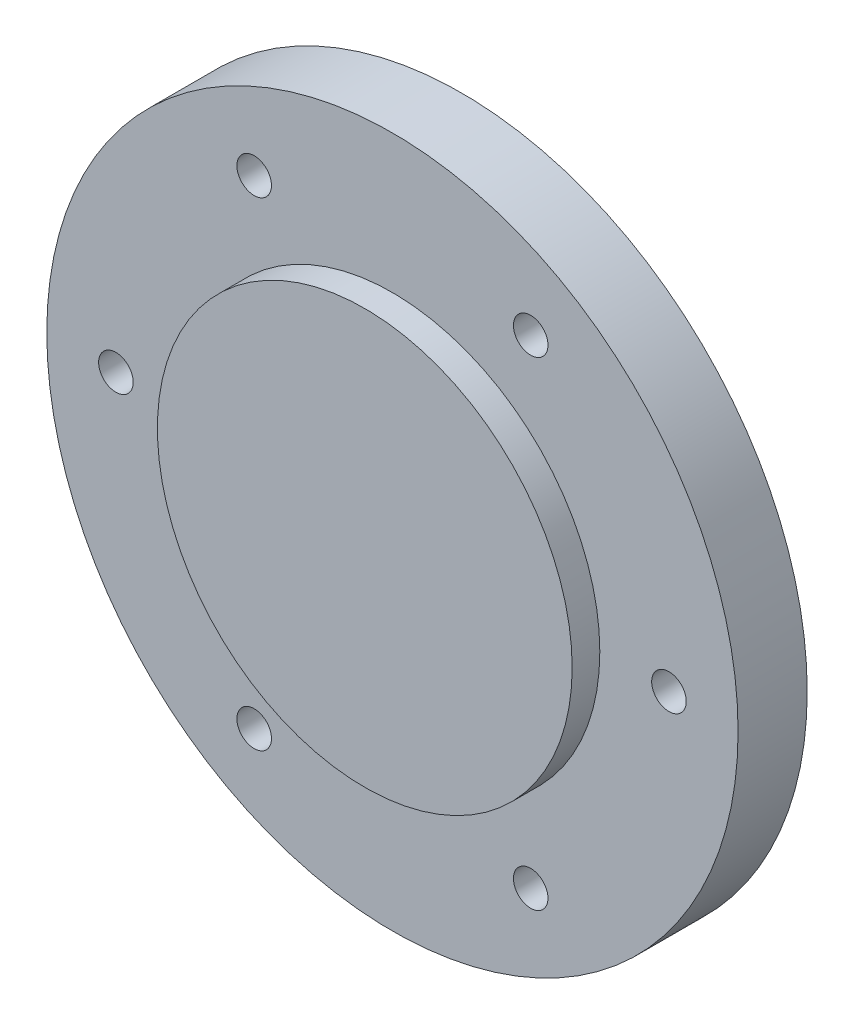
SolidWorks part; units mm, degrees
ref_plane "Front Plane" through (0, 0, 0) normal (0, 0, 1) x (1, 0, 0)
ref_plane "Top Plane" through (0, 0, 0) normal (0, 1, 0) x (1, 0, 0)
ref_plane "Right Plane" through (0, 0, 0) normal (1, 0, 0) x (0, 0, -1)
sketch "SK_Disc" plane through (0, 0, 0) normal (0, 0, 1) x (1, 0, 0)
  circle A0 centre (0, 0) radius 25
  dimension "D_disc" = 50
extrude "Output_Disc" add sketch "SK_Disc" along normal blind 5
ref_plane "PL_Mount" through (0, 0, 5) normal (0, 0, 1) x (1, 0, 0)
sketch "SK_Pilot" plane through (0, 0, 5) normal (0, 0, 1) x (1, 0, 0)
  circle A0 centre (0, 0) radius 15
  dimension "D_pil" = 30
extrude "Pilot_Boss" add sketch "SK_Pilot" along normal blind 2
sketch "SK_OutHole" plane through (0, 0, 5) normal (0, 0, 1) x (1, 0, 0)
  circle A0 centre (20, 0) radius 1.25
  dimension "D_oh" = 2.5
  dimension "R_oh" = 20
extrude "Output_Tapped_Hole" cut sketch "SK_OutHole" against normal blind 5
ref_axis "AX_Joint" through (0, 0, -0.35) along (0, 0, 1)
pattern_circular "Output_Hole_Pattern" count 6 over 360 about axis through (0, 0, -0.35) along (0, 0, 1) of "Output_Tapped_Hole"
equation "\"D_out\" = 50"
equation "\"T_out\" = 5"
equation "\"PCD_out\" = 40"
equation "\"D_pilot\" = 30"
equation "\"H_pilot\" = 2"
equation "\"D_out_hole\" = 2.5"
equation "\"D_disc@SK_Disc\" = \"D_out\""
equation "\"D1@Output_Disc\" = \"T_out\""
equation "\"D_pil@SK_Pilot\" = \"D_pilot\""
equation "\"D1@Pilot_Boss\" = \"H_pilot\""
equation "\"D_oh@SK_OutHole\" = \"D_out_hole\""
equation "\"R_oh@SK_OutHole\" = \"PCD_out\"/2"
